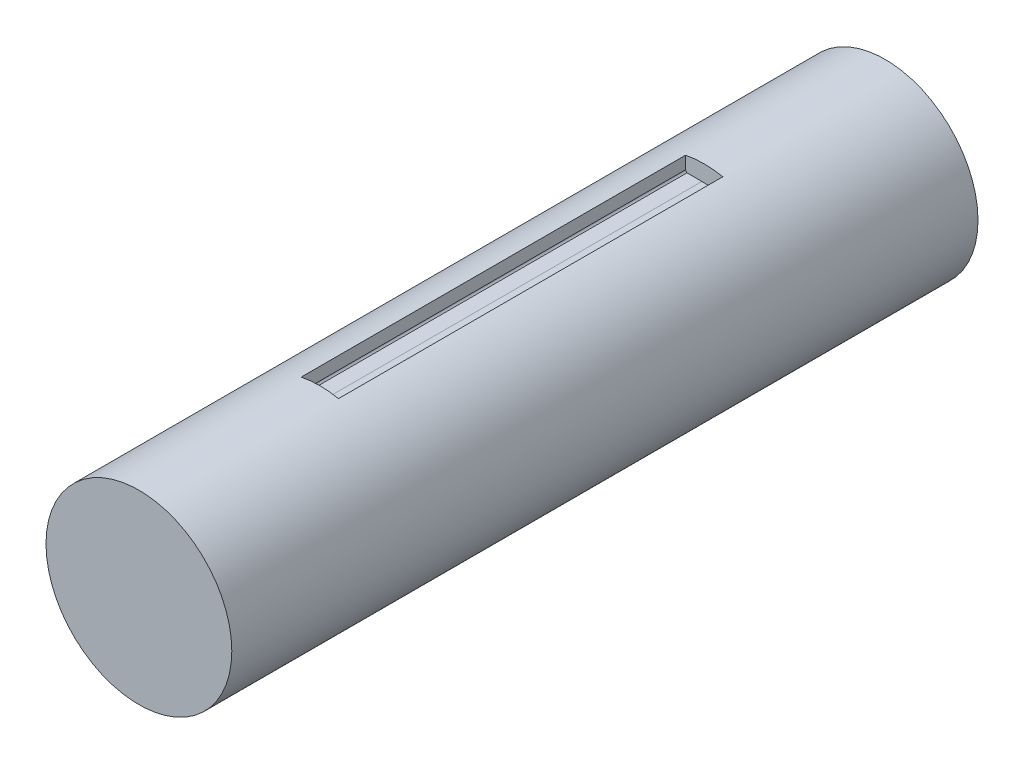
SolidWorks part; units mm, degrees
ref_plane "Ön Düzlem" through (0, 0, 0) normal (0, 0, 1) x (1, 0, 0)
ref_plane "Üst Düzlem" through (0, 0, 0) normal (0, 1, 0) x (1, 0, 0)
ref_plane "Sağ Düzlem" through (0, 0, 0) normal (1, 0, 0) x (0, 0, -1)
sketch "Model" plane through (0, 0, 0) normal (0, 0, 1) x (1, 0, 0)
  line L0 (-9.5, 79.7049) -> (9.5, 79.7049)
  line L1 (60.5945, 121.4987) -> (60.8885, 121.3363)
  line L2 (60.8885, 121.3363) -> (61.139, 121.1124)
  line L3 (61.139, 121.1124) -> (61.3334, 120.8385)
  line L4 (61.3334, 120.8385) -> (61.4619, 120.5282)
  line L5 (61.4619, 120.5282) -> (61.5182, 120.197)
  line L6 (61.5182, 120.197) -> (61.4993, 119.8617)
  line L7 (61.4993, 119.8617) -> (61.4063, 119.5389)
  line L8 (61.4063, 119.5389) -> (45.7726, 92.4605)
  line L9 (45.7726, 92.4605) -> (42.0525, 92.3778)
  line L10 (42.0525, 92.3778) -> (41.4785, 90.992)
  line L11 (58.0621, 81.4174) -> (58.9753, 82.6074)
  line L12 (58.9753, 82.6074) -> (57.1868, 85.8705)
  line L13 (57.1868, 85.8705) -> (72.8206, 112.9489)
  line L14 (72.8206, 112.9489) -> (73.0536, 113.1908)
  line L15 (73.0536, 113.1908) -> (73.3346, 113.3748)
  line L16 (73.3346, 113.3748) -> (73.6495, 113.4917)
  line L17 (73.6495, 113.4917) -> (73.9825, 113.5355)
  line L18 (73.9825, 113.5355) -> (74.317, 113.5041)
  line L19 (74.317, 113.5041) -> (74.636, 113.3991)
  line L20 (74.636, 113.3991) -> (74.9237, 113.2258)
  line L21 (74.9237, 113.2258) -> (89.976, 101.6758)
  line L22 (89.976, 101.6758) -> (90.2179, 101.4427)
  line L23 (90.2179, 101.4427) -> (90.4019, 101.1617)
  line L24 (90.4019, 101.1617) -> (90.5188, 100.8468)
  line L25 (90.5188, 100.8468) -> (90.5626, 100.5138)
  line L26 (90.5626, 100.5138) -> (90.5313, 100.1793)
  line L27 (90.5313, 100.1793) -> (90.4263, 99.8603)
  line L28 (90.4263, 99.8603) -> (90.2529, 99.5726)
  line L29 (90.2529, 99.5726) -> (68.1435, 77.4631)
  line L30 (68.1435, 77.4631) -> (64.5287, 78.3461)
  line L31 (64.5287, 78.3461) -> (63.6156, 77.1561)
  line L32 (77.1561, 63.6156) -> (78.3461, 64.5287)
  line L33 (78.3461, 64.5287) -> (77.4631, 68.1435)
  line L34 (77.4631, 68.1435) -> (99.5726, 90.2529)
  line L35 (99.5726, 90.2529) -> (99.8603, 90.4263)
  line L36 (99.8603, 90.4263) -> (100.1793, 90.5313)
  line L37 (100.1793, 90.5313) -> (100.5138, 90.5626)
  line L38 (100.5138, 90.5626) -> (100.8468, 90.5188)
  line L39 (100.8468, 90.5188) -> (101.1617, 90.4019)
  line L40 (101.1617, 90.4019) -> (101.4427, 90.2179)
  line L41 (101.4427, 90.2179) -> (101.6758, 89.976)
  line L42 (101.6758, 89.976) -> (113.2258, 74.9237)
  line L43 (113.2258, 74.9237) -> (113.3991, 74.636)
  line L44 (113.3991, 74.636) -> (113.5041, 74.317)
  line L45 (113.5041, 74.317) -> (113.5355, 73.9825)
  line L46 (113.5355, 73.9825) -> (113.4917, 73.6495)
  line L47 (113.4917, 73.6495) -> (113.3748, 73.3346)
  line L48 (113.3748, 73.3346) -> (113.1908, 73.0536)
  line L49 (113.1908, 73.0536) -> (112.9489, 72.8206)
  line L50 (112.9489, 72.8206) -> (85.8705, 57.1868)
  line L51 (85.8705, 57.1868) -> (82.6074, 58.9753)
  line L52 (82.6074, 58.9753) -> (81.4174, 58.0621)
  line L53 (90.992, 41.4785) -> (92.3778, 42.0525)
  line L54 (92.3778, 42.0525) -> (92.4605, 45.7726)
  line L55 (92.4605, 45.7726) -> (119.5389, 61.4063)
  line L56 (119.5389, 61.4063) -> (119.8617, 61.4993)
  line L57 (119.8617, 61.4993) -> (120.197, 61.5182)
  line L58 (120.197, 61.5182) -> (120.5282, 61.4619)
  line L59 (120.5282, 61.4619) -> (120.8385, 61.3334)
  line L60 (120.8385, 61.3334) -> (121.1124, 61.139)
  line L61 (121.1124, 61.139) -> (121.3363, 60.8885)
  line L62 (121.3363, 60.8885) -> (121.4987, 60.5945)
  line L63 (121.4987, 60.5945) -> (128.7594, 43.0658)
  line L64 (128.7594, 43.0658) -> (128.8524, 42.743)
  line L65 (128.8524, 42.743) -> (128.8712, 42.4076)
  line L66 (128.8712, 42.4076) -> (128.815, 42.0765)
  line L67 (128.815, 42.0765) -> (128.6864, 41.7662)
  line L68 (128.6864, 41.7662) -> (128.492, 41.4922)
  line L69 (128.492, 41.4922) -> (128.2416, 41.2684)
  line L70 (128.2416, 41.2684) -> (127.9476, 41.1059)
  line L71 (127.9476, 41.1059) -> (97.7455, 33.0133)
  line L72 (97.7455, 33.0133) -> (95.0566, 35.5853)
  line L73 (95.0566, 35.5853) -> (93.6707, 35.0113)
  line L74 (98.6269, 16.5147) -> (100.1141, 16.7105)
  line L75 (100.1141, 16.7105) -> (101.1568, 20.2824)
  line L76 (101.1568, 20.2824) -> (131.3588, 28.375)
  line L77 (131.3588, 28.375) -> (131.6947, 28.3813)
  line L78 (131.6947, 28.3813) -> (132.0235, 28.3127)
  line L79 (132.0235, 28.3127) -> (132.3288, 28.1726)
  line L80 (132.3288, 28.1726) -> (132.5953, 27.9682)
  line L81 (132.5953, 27.9682) -> (132.8096, 27.7095)
  line L82 (132.8096, 27.7095) -> (132.9609, 27.4097)
  line L83 (132.9609, 27.4097) -> (133.0418, 27.0836)
  line L84 (133.0418, 27.0836) -> (135.5183, 8.273)
  line L85 (135.5183, 8.273) -> (135.5246, 7.9371)
  line L86 (135.5246, 7.9371) -> (135.4559, 7.6083)
  line L87 (135.4559, 7.6083) -> (135.3159, 7.303)
  line L88 (135.3159, 7.303) -> (135.1114, 7.0365)
  line L89 (135.1114, 7.0365) -> (134.8528, 6.8222)
  line L90 (134.8528, 6.8222) -> (134.5529, 6.6709)
  line L91 (134.5529, 6.6709) -> (134.2269, 6.59)
  line L92 (134.2269, 6.59) -> (102.9594, 6.59)
  line L93 (102.9594, 6.59) -> (101.0278, 9.7704)
  line L94 (101.0278, 9.7704) -> (99.5406, 9.5746)
  line L95 (99.5406, -9.5746) -> (101.0278, -9.7704)
  line L96 (101.0278, -9.7704) -> (102.9594, -6.59)
  line L97 (102.9594, -6.59) -> (134.2269, -6.59)
  line L98 (134.2269, -6.59) -> (134.5529, -6.6709)
  line L99 (134.5529, -6.6709) -> (134.8528, -6.8222)
  line L100 (134.8528, -6.8222) -> (135.1114, -7.0365)
  line L101 (135.1114, -7.0365) -> (135.3159, -7.303)
  line L102 (135.3159, -7.303) -> (135.4559, -7.6083)
  line L103 (135.4559, -7.6083) -> (135.5246, -7.9371)
  line L104 (135.5246, -7.9371) -> (135.5183, -8.273)
  line L105 (135.5183, -8.273) -> (133.0418, -27.0836)
  line L106 (133.0418, -27.0836) -> (132.9609, -27.4097)
  line L107 (132.9609, -27.4097) -> (132.8096, -27.7095)
  line L108 (132.8096, -27.7095) -> (132.5953, -27.9682)
  line L109 (132.5953, -27.9682) -> (132.3288, -28.1726)
  line L110 (132.3288, -28.1726) -> (132.0235, -28.3127)
  line L111 (132.0235, -28.3127) -> (131.6947, -28.3813)
  line L112 (131.6947, -28.3813) -> (131.3588, -28.375)
  line L113 (131.3588, -28.375) -> (101.1568, -20.2824)
  line L114 (101.1568, -20.2824) -> (100.1141, -16.7105)
  line L115 (100.1141, -16.7105) -> (98.6269, -16.5147)
  line L116 (93.6707, -35.0113) -> (95.0566, -35.5853)
  line L117 (95.0566, -35.5853) -> (97.7455, -33.0133)
  line L118 (97.7455, -33.0133) -> (127.9476, -41.1059)
  line L119 (127.9476, -41.1059) -> (128.2416, -41.2684)
  line L120 (128.2416, -41.2684) -> (128.492, -41.4922)
  line L121 (128.492, -41.4922) -> (128.6864, -41.7662)
  line L122 (128.6864, -41.7662) -> (128.815, -42.0765)
  line L123 (128.815, -42.0765) -> (128.8712, -42.4076)
  line L124 (128.8712, -42.4076) -> (128.8524, -42.743)
  line L125 (128.8524, -42.743) -> (128.7594, -43.0658)
  line L126 (128.7594, -43.0658) -> (121.4987, -60.5945)
  line L127 (121.4987, -60.5945) -> (121.3363, -60.8885)
  line L128 (121.3363, -60.8885) -> (121.1124, -61.139)
  line L129 (121.1124, -61.139) -> (120.8385, -61.3334)
  line L130 (120.8385, -61.3334) -> (120.5282, -61.4619)
  line L131 (120.5282, -61.4619) -> (120.197, -61.5182)
  line L132 (120.197, -61.5182) -> (119.8617, -61.4993)
  line L133 (119.8617, -61.4993) -> (119.5389, -61.4063)
  line L134 (119.5389, -61.4063) -> (92.4605, -45.7726)
  line L135 (92.4605, -45.7726) -> (92.3778, -42.0525)
  line L136 (92.3778, -42.0525) -> (90.992, -41.4785)
  line L137 (81.4174, -58.0621) -> (82.6074, -58.9753)
  line L138 (82.6074, -58.9753) -> (85.8705, -57.1868)
  line L139 (85.8705, -57.1868) -> (112.9489, -72.8206)
  line L140 (112.9489, -72.8206) -> (113.1908, -73.0536)
  line L141 (113.1908, -73.0536) -> (113.3748, -73.3346)
  line L142 (113.3748, -73.3346) -> (113.4917, -73.6495)
  line L143 (113.4917, -73.6495) -> (113.5355, -73.9825)
  line L144 (113.5355, -73.9825) -> (113.5041, -74.317)
  line L145 (113.5041, -74.317) -> (113.3991, -74.636)
  line L146 (113.3991, -74.636) -> (113.2258, -74.9237)
  line L147 (113.2258, -74.9237) -> (101.6758, -89.976)
  line L148 (101.6758, -89.976) -> (101.4427, -90.2179)
  line L149 (101.4427, -90.2179) -> (101.1617, -90.4019)
  line L150 (101.1617, -90.4019) -> (100.8468, -90.5188)
  line L151 (100.8468, -90.5188) -> (100.5138, -90.5626)
  line L152 (100.5138, -90.5626) -> (100.1793, -90.5313)
  line L153 (100.1793, -90.5313) -> (99.8603, -90.4263)
  line L154 (99.8603, -90.4263) -> (99.5726, -90.2529)
  line L155 (99.5726, -90.2529) -> (77.4631, -68.1435)
  line L156 (77.4631, -68.1435) -> (78.3461, -64.5287)
  line L157 (78.3461, -64.5287) -> (77.1561, -63.6156)
  line L158 (63.6156, -77.1561) -> (64.5287, -78.3461)
  line L159 (64.5287, -78.3461) -> (68.1435, -77.4631)
  line L160 (68.1435, -77.4631) -> (90.2529, -99.5726)
  line L161 (90.2529, -99.5726) -> (90.4263, -99.8603)
  line L162 (90.4263, -99.8603) -> (90.5313, -100.1793)
  line L163 (90.5313, -100.1793) -> (90.5626, -100.5138)
  line L164 (90.5626, -100.5138) -> (90.5188, -100.8468)
  line L165 (90.5188, -100.8468) -> (90.4019, -101.1617)
  line L166 (90.4019, -101.1617) -> (90.2179, -101.4427)
  line L167 (90.2179, -101.4427) -> (89.976, -101.6758)
  line L168 (89.976, -101.6758) -> (74.9237, -113.2258)
  line L169 (74.9237, -113.2258) -> (74.636, -113.3991)
  line L170 (74.636, -113.3991) -> (74.317, -113.5041)
  line L171 (74.317, -113.5041) -> (73.9825, -113.5355)
  line L172 (73.9825, -113.5355) -> (73.6495, -113.4917)
  line L173 (73.6495, -113.4917) -> (73.3346, -113.3748)
  line L174 (73.3346, -113.3748) -> (73.0536, -113.1908)
  line L175 (73.0536, -113.1908) -> (72.8206, -112.9489)
  line L176 (72.8206, -112.9489) -> (57.1868, -85.8705)
  line L177 (57.1868, -85.8705) -> (58.9753, -82.6074)
  line L178 (58.9753, -82.6074) -> (58.0621, -81.4174)
  line L179 (41.4785, -90.992) -> (42.0525, -92.3778)
  line L180 (42.0525, -92.3778) -> (45.7726, -92.4605)
  line L181 (45.7726, -92.4605) -> (61.4063, -119.5389)
  line L182 (61.4063, -119.5389) -> (61.4993, -119.8617)
  line L183 (61.4993, -119.8617) -> (61.5182, -120.197)
  line L184 (61.5182, -120.197) -> (61.4619, -120.5282)
  line L185 (61.4619, -120.5282) -> (61.3334, -120.8385)
  line L186 (61.3334, -120.8385) -> (61.139, -121.1124)
  line L187 (61.139, -121.1124) -> (60.8885, -121.3363)
  line L188 (60.8885, -121.3363) -> (60.5945, -121.4987)
  line L189 (60.5945, -121.4987) -> (43.0658, -128.7594)
  line L190 (43.0658, -128.7594) -> (42.743, -128.8524)
  line L191 (42.743, -128.8524) -> (42.4076, -128.8712)
  line L192 (42.4076, -128.8712) -> (42.0765, -128.815)
  line L193 (42.0765, -128.815) -> (41.7662, -128.6864)
  line L194 (41.7662, -128.6864) -> (41.4922, -128.492)
  line L195 (41.4922, -128.492) -> (41.2684, -128.2416)
  line L196 (41.2684, -128.2416) -> (41.1059, -127.9476)
  line L197 (41.1059, -127.9476) -> (33.0133, -97.7455)
  line L198 (33.0133, -97.7455) -> (35.5853, -95.0566)
  line L199 (35.5853, -95.0566) -> (35.0113, -93.6707)
  line L200 (16.5147, -98.6269) -> (16.7105, -100.1141)
  line L201 (16.7105, -100.1141) -> (20.2824, -101.1568)
  line L202 (20.2824, -101.1568) -> (28.375, -131.3588)
  line L203 (28.375, -131.3588) -> (28.3813, -131.6947)
  line L204 (28.3813, -131.6947) -> (28.3127, -132.0235)
  line L205 (28.3127, -132.0235) -> (28.1726, -132.3288)
  line L206 (28.1726, -132.3288) -> (27.9682, -132.5953)
  line L207 (27.9682, -132.5953) -> (27.7095, -132.8096)
  line L208 (27.7095, -132.8096) -> (27.4097, -132.9609)
  line L209 (27.4097, -132.9609) -> (27.0836, -133.0418)
  line L210 (27.0836, -133.0418) -> (8.273, -135.5183)
  line L211 (8.273, -135.5183) -> (7.9371, -135.5246)
  line L212 (7.9371, -135.5246) -> (7.6083, -135.4559)
  line L213 (7.6083, -135.4559) -> (7.303, -135.3159)
  line L214 (7.303, -135.3159) -> (7.0365, -135.1114)
  line L215 (7.0365, -135.1114) -> (6.8222, -134.8528)
  line L216 (6.8222, -134.8528) -> (6.6709, -134.5529)
  line L217 (6.6709, -134.5529) -> (6.59, -134.2269)
  line L218 (6.59, -134.2269) -> (6.59, -102.9594)
  line L219 (6.59, -102.9594) -> (9.7704, -101.0278)
  line L220 (9.7704, -101.0278) -> (9.5746, -99.5406)
  line L221 (-9.5746, -99.5406) -> (-9.7704, -101.0278)
  line L222 (-9.7704, -101.0278) -> (-6.59, -102.9594)
  line L223 (-6.59, -102.9594) -> (-6.59, -134.2269)
  line L224 (-6.59, -134.2269) -> (-6.6709, -134.5529)
  line L225 (-6.6709, -134.5529) -> (-6.8222, -134.8528)
  line L226 (-6.8222, -134.8528) -> (-7.0365, -135.1114)
  line L227 (-7.0365, -135.1114) -> (-7.303, -135.3159)
  line L228 (-7.303, -135.3159) -> (-7.6083, -135.4559)
  line L229 (-7.6083, -135.4559) -> (-7.9371, -135.5246)
  line L230 (-7.9371, -135.5246) -> (-8.273, -135.5183)
  line L231 (-8.273, -135.5183) -> (-27.0836, -133.0418)
  line L232 (-27.0836, -133.0418) -> (-27.4097, -132.9609)
  line L233 (-27.4097, -132.9609) -> (-27.7095, -132.8096)
  line L234 (-27.7095, -132.8096) -> (-27.9682, -132.5953)
  line L235 (-27.9682, -132.5953) -> (-28.1726, -132.3288)
  line L236 (-28.1726, -132.3288) -> (-28.3127, -132.0235)
  line L237 (-28.3127, -132.0235) -> (-28.3813, -131.6947)
  line L238 (-28.3813, -131.6947) -> (-28.375, -131.3588)
  line L239 (-28.375, -131.3588) -> (-20.2824, -101.1568)
  line L240 (-20.2824, -101.1568) -> (-16.7105, -100.1141)
  line L241 (-16.7105, -100.1141) -> (-16.5147, -98.6269)
  line L242 (-35.0113, -93.6707) -> (-35.5853, -95.0566)
  line L243 (-35.5853, -95.0566) -> (-33.0133, -97.7455)
  line L244 (-33.0133, -97.7455) -> (-41.1059, -127.9476)
  line L245 (-41.1059, -127.9476) -> (-41.2684, -128.2416)
  line L246 (-41.2684, -128.2416) -> (-41.4922, -128.492)
  line L247 (-41.4922, -128.492) -> (-41.7662, -128.6864)
  line L248 (-41.7662, -128.6864) -> (-42.0765, -128.815)
  line L249 (-42.0765, -128.815) -> (-42.4076, -128.8712)
  line L250 (-42.4076, -128.8712) -> (-42.743, -128.8524)
  line L251 (-42.743, -128.8524) -> (-43.0658, -128.7594)
  line L252 (-43.0658, -128.7594) -> (-60.5945, -121.4987)
  line L253 (-60.5945, -121.4987) -> (-60.8885, -121.3363)
  line L254 (-60.8885, -121.3363) -> (-61.139, -121.1124)
  line L255 (-61.139, -121.1124) -> (-61.3334, -120.8385)
  line L256 (-61.3334, -120.8385) -> (-61.4619, -120.5282)
  line L257 (-61.4619, -120.5282) -> (-61.5182, -120.197)
  line L258 (-61.5182, -120.197) -> (-61.4993, -119.8617)
  line L259 (-61.4993, -119.8617) -> (-61.4063, -119.5389)
  line L260 (-61.4063, -119.5389) -> (-45.7726, -92.4605)
  line L261 (-45.7726, -92.4605) -> (-42.0525, -92.3778)
  line L262 (-42.0525, -92.3778) -> (-41.4785, -90.992)
  line L263 (-58.0621, -81.4174) -> (-58.9753, -82.6074)
  line L264 (-58.9753, -82.6074) -> (-57.1868, -85.8705)
  line L265 (-57.1868, -85.8705) -> (-72.8206, -112.9489)
  line L266 (-72.8206, -112.9489) -> (-73.0536, -113.1908)
  line L267 (-73.0536, -113.1908) -> (-73.3346, -113.3748)
  line L268 (-73.3346, -113.3748) -> (-73.6495, -113.4917)
  line L269 (-73.6495, -113.4917) -> (-73.9825, -113.5355)
  line L270 (-73.9825, -113.5355) -> (-74.317, -113.5041)
  line L271 (-74.317, -113.5041) -> (-74.636, -113.3991)
  line L272 (-74.636, -113.3991) -> (-74.9237, -113.2258)
  line L273 (-74.9237, -113.2258) -> (-89.976, -101.6758)
  line L274 (-89.976, -101.6758) -> (-90.2179, -101.4427)
  line L275 (-90.2179, -101.4427) -> (-90.4019, -101.1617)
  line L276 (-90.4019, -101.1617) -> (-90.5188, -100.8468)
  line L277 (-90.5188, -100.8468) -> (-90.5626, -100.5138)
  line L278 (-90.5626, -100.5138) -> (-90.5313, -100.1793)
  line L279 (-90.5313, -100.1793) -> (-90.4263, -99.8603)
  line L280 (-90.4263, -99.8603) -> (-90.2529, -99.5726)
  line L281 (-90.2529, -99.5726) -> (-68.1435, -77.4631)
  line L282 (-68.1435, -77.4631) -> (-64.5287, -78.3461)
  line L283 (-64.5287, -78.3461) -> (-63.6156, -77.1561)
  line L284 (-77.1561, -63.6156) -> (-78.3461, -64.5287)
  line L285 (-78.3461, -64.5287) -> (-77.4631, -68.1435)
  line L286 (-77.4631, -68.1435) -> (-99.5726, -90.2529)
  line L287 (-99.5726, -90.2529) -> (-99.8603, -90.4263)
  line L288 (-99.8603, -90.4263) -> (-100.1793, -90.5313)
  line L289 (-100.1793, -90.5313) -> (-100.5138, -90.5626)
  line L290 (-100.5138, -90.5626) -> (-100.8468, -90.5188)
  line L291 (-100.8468, -90.5188) -> (-101.1617, -90.4019)
  line L292 (-101.1617, -90.4019) -> (-101.4427, -90.2179)
  line L293 (-101.4427, -90.2179) -> (-101.6758, -89.976)
  line L294 (-101.6758, -89.976) -> (-113.2258, -74.9237)
  line L295 (-113.2258, -74.9237) -> (-113.3991, -74.636)
  line L296 (-113.3991, -74.636) -> (-113.5041, -74.317)
  line L297 (-113.5041, -74.317) -> (-113.5355, -73.9825)
  line L298 (-113.5355, -73.9825) -> (-113.4917, -73.6495)
  line L299 (-113.4917, -73.6495) -> (-113.3748, -73.3346)
  line L300 (-113.3748, -73.3346) -> (-113.1908, -73.0536)
  line L301 (-113.1908, -73.0536) -> (-112.9489, -72.8206)
  line L302 (-112.9489, -72.8206) -> (-85.8705, -57.1868)
  line L303 (-85.8705, -57.1868) -> (-82.6074, -58.9753)
  line L304 (-82.6074, -58.9753) -> (-81.4174, -58.0621)
  line L305 (-90.992, -41.4785) -> (-92.3778, -42.0525)
  line L306 (-92.3778, -42.0525) -> (-92.4605, -45.7726)
  line L307 (-92.4605, -45.7726) -> (-119.5389, -61.4063)
  line L308 (-119.5389, -61.4063) -> (-119.8617, -61.4993)
  line L309 (-119.8617, -61.4993) -> (-120.197, -61.5182)
  line L310 (-120.197, -61.5182) -> (-120.5282, -61.4619)
  line L311 (-120.5282, -61.4619) -> (-120.8385, -61.3334)
  line L312 (-120.8385, -61.3334) -> (-121.1124, -61.139)
  line L313 (-121.1124, -61.139) -> (-121.3363, -60.8885)
  line L314 (-121.3363, -60.8885) -> (-121.4987, -60.5945)
  line L315 (-121.4987, -60.5945) -> (-128.7594, -43.0658)
  line L316 (-128.7594, -43.0658) -> (-128.8524, -42.743)
  line L317 (-128.8524, -42.743) -> (-128.8712, -42.4076)
  line L318 (-128.8712, -42.4076) -> (-128.815, -42.0765)
  line L319 (-128.815, -42.0765) -> (-128.6864, -41.7662)
  line L320 (-128.6864, -41.7662) -> (-128.492, -41.4922)
  line L321 (-128.492, -41.4922) -> (-128.2416, -41.2684)
  line L322 (-128.2416, -41.2684) -> (-127.9476, -41.1059)
  line L323 (-127.9476, -41.1059) -> (-97.7455, -33.0133)
  line L324 (-97.7455, -33.0133) -> (-95.0566, -35.5853)
  line L325 (-95.0566, -35.5853) -> (-93.6707, -35.0113)
  line L326 (-98.6269, -16.5147) -> (-100.1141, -16.7105)
  line L327 (-100.1141, -16.7105) -> (-101.1568, -20.2824)
  line L328 (-101.1568, -20.2824) -> (-131.3588, -28.375)
  line L329 (-131.3588, -28.375) -> (-131.6947, -28.3813)
  line L330 (-131.6947, -28.3813) -> (-132.0235, -28.3127)
  line L331 (-132.0235, -28.3127) -> (-132.3288, -28.1726)
  line L332 (-132.3288, -28.1726) -> (-132.5953, -27.9682)
  line L333 (-132.5953, -27.9682) -> (-132.8096, -27.7095)
  line L334 (-132.8096, -27.7095) -> (-132.9609, -27.4097)
  line L335 (-132.9609, -27.4097) -> (-133.0418, -27.0836)
  line L336 (-133.0418, -27.0836) -> (-135.5183, -8.273)
  line L337 (-135.5183, -8.273) -> (-135.5246, -7.9371)
  line L338 (-135.5246, -7.9371) -> (-135.4559, -7.6083)
  line L339 (-135.4559, -7.6083) -> (-135.3159, -7.303)
  line L340 (-135.3159, -7.303) -> (-135.1114, -7.0365)
  line L341 (-135.1114, -7.0365) -> (-134.8528, -6.8222)
  line L342 (-134.8528, -6.8222) -> (-134.5529, -6.6709)
  line L343 (-134.5529, -6.6709) -> (-134.2269, -6.59)
  line L344 (-134.2269, -6.59) -> (-102.9594, -6.59)
  line L345 (-102.9594, -6.59) -> (-101.0278, -9.7704)
  line L346 (-101.0278, -9.7704) -> (-99.5406, -9.5746)
  line L347 (-99.5406, 9.5746) -> (-101.0278, 9.7704)
  line L348 (-101.0278, 9.7704) -> (-102.9594, 6.59)
  line L349 (-102.9594, 6.59) -> (-134.2269, 6.59)
  line L350 (-134.2269, 6.59) -> (-134.5529, 6.6709)
  line L351 (-134.5529, 6.6709) -> (-134.8528, 6.8222)
  line L352 (-134.8528, 6.8222) -> (-135.1114, 7.0365)
  line L353 (-135.1114, 7.0365) -> (-135.3159, 7.303)
  line L354 (-135.3159, 7.303) -> (-135.4559, 7.6083)
  line L355 (-135.4559, 7.6083) -> (-135.5246, 7.9371)
  line L356 (-135.5246, 7.9371) -> (-135.5183, 8.273)
  line L357 (-135.5183, 8.273) -> (-133.0418, 27.0836)
  line L358 (-133.0418, 27.0836) -> (-132.9609, 27.4097)
  line L359 (-132.9609, 27.4097) -> (-132.8096, 27.7095)
  line L360 (-132.8096, 27.7095) -> (-132.5953, 27.9682)
  line L361 (-132.5953, 27.9682) -> (-132.3288, 28.1726)
  line L362 (-132.3288, 28.1726) -> (-132.0235, 28.3127)
  line L363 (-132.0235, 28.3127) -> (-131.6947, 28.3813)
  line L364 (-131.6947, 28.3813) -> (-131.3588, 28.375)
  line L365 (-131.3588, 28.375) -> (-101.1568, 20.2824)
  line L366 (-101.1568, 20.2824) -> (-100.1141, 16.7105)
  line L367 (-100.1141, 16.7105) -> (-98.6269, 16.5147)
  line L368 (-93.6707, 35.0113) -> (-95.0566, 35.5853)
  line L369 (-95.0566, 35.5853) -> (-97.7455, 33.0133)
  line L370 (-97.7455, 33.0133) -> (-127.9476, 41.1059)
  line L371 (-127.9476, 41.1059) -> (-128.2416, 41.2684)
  line L372 (-128.2416, 41.2684) -> (-128.492, 41.4922)
  line L373 (-128.492, 41.4922) -> (-128.6864, 41.7662)
  line L374 (-128.6864, 41.7662) -> (-128.815, 42.0765)
  line L375 (-128.815, 42.0765) -> (-128.8712, 42.4076)
  line L376 (-128.8712, 42.4076) -> (-128.8524, 42.743)
  line L377 (-128.8524, 42.743) -> (-128.7594, 43.0658)
  line L378 (-128.7594, 43.0658) -> (-121.4987, 60.5945)
  line L379 (-121.4987, 60.5945) -> (-121.3363, 60.8885)
  line L380 (-121.3363, 60.8885) -> (-121.1124, 61.139)
  line L381 (-121.1124, 61.139) -> (-120.8385, 61.3334)
  line L382 (-120.8385, 61.3334) -> (-120.5282, 61.4619)
  line L383 (-120.5282, 61.4619) -> (-120.197, 61.5182)
  line L384 (-120.197, 61.5182) -> (-119.8617, 61.4993)
  line L385 (-119.8617, 61.4993) -> (-119.5389, 61.4063)
  line L386 (-119.5389, 61.4063) -> (-92.4605, 45.7726)
  line L387 (-92.4605, 45.7726) -> (-92.3778, 42.0525)
  line L388 (-92.3778, 42.0525) -> (-90.992, 41.4785)
  line L389 (-81.4174, 58.0621) -> (-82.6074, 58.9753)
  line L390 (-82.6074, 58.9753) -> (-85.8705, 57.1868)
  line L391 (-85.8705, 57.1868) -> (-112.9489, 72.8206)
  line L392 (-112.9489, 72.8206) -> (-113.1908, 73.0536)
  line L393 (-113.1908, 73.0536) -> (-113.3748, 73.3346)
  line L394 (-113.3748, 73.3346) -> (-113.4917, 73.6495)
  line L395 (-113.4917, 73.6495) -> (-113.5355, 73.9825)
  line L396 (-113.5355, 73.9825) -> (-113.5041, 74.317)
  line L397 (-113.5041, 74.317) -> (-113.3991, 74.636)
  line L398 (-113.3991, 74.636) -> (-113.2258, 74.9237)
  line L399 (-113.2258, 74.9237) -> (-101.6758, 89.976)
  line L400 (-101.6758, 89.976) -> (-101.4427, 90.2179)
  line L401 (-101.4427, 90.2179) -> (-101.1617, 90.4019)
  line L402 (-101.1617, 90.4019) -> (-100.8468, 90.5188)
  line L403 (-100.8468, 90.5188) -> (-100.5138, 90.5626)
  line L404 (-100.5138, 90.5626) -> (-100.1793, 90.5313)
  line L405 (-100.1793, 90.5313) -> (-99.8603, 90.4263)
  line L406 (-99.8603, 90.4263) -> (-99.5726, 90.2529)
  line L407 (-99.5726, 90.2529) -> (-77.4631, 68.1435)
  line L408 (-77.4631, 68.1435) -> (-78.3461, 64.5287)
  line L409 (-78.3461, 64.5287) -> (-77.1561, 63.6156)
  line L410 (-63.6156, 77.1561) -> (-64.5287, 78.3461)
  line L411 (-64.5287, 78.3461) -> (-68.1435, 77.4631)
  line L412 (-68.1435, 77.4631) -> (-90.2529, 99.5726)
  line L413 (-90.2529, 99.5726) -> (-90.4263, 99.8603)
  line L414 (-90.4263, 99.8603) -> (-90.5313, 100.1793)
  line L415 (-90.5313, 100.1793) -> (-90.5626, 100.5138)
  line L416 (-90.5626, 100.5138) -> (-90.5188, 100.8468)
  line L417 (-90.5188, 100.8468) -> (-90.4019, 101.1617)
  line L418 (-90.4019, 101.1617) -> (-90.2179, 101.4427)
  line L419 (-90.2179, 101.4427) -> (-89.976, 101.6758)
  line L420 (-89.976, 101.6758) -> (-74.9237, 113.2258)
  line L421 (-74.9237, 113.2258) -> (-74.636, 113.3991)
  line L422 (-74.636, 113.3991) -> (-74.317, 113.5041)
  line L423 (-74.317, 113.5041) -> (-73.9825, 113.5355)
  line L424 (-73.9825, 113.5355) -> (-73.6495, 113.4917)
  line L425 (-73.6495, 113.4917) -> (-73.3346, 113.3748)
  line L426 (-73.3346, 113.3748) -> (-73.0536, 113.1908)
  line L427 (-73.0536, 113.1908) -> (-72.8206, 112.9489)
  line L428 (-72.8206, 112.9489) -> (-57.1868, 85.8705)
  line L429 (-57.1868, 85.8705) -> (-58.9753, 82.6074)
  line L430 (-58.9753, 82.6074) -> (-58.0621, 81.4174)
  line L431 (-41.4785, 90.992) -> (-42.0525, 92.3778)
  line L432 (-42.0525, 92.3778) -> (-45.7726, 92.4605)
  line L433 (-45.7726, 92.4605) -> (-61.4063, 119.5389)
  line L434 (-61.4063, 119.5389) -> (-61.4993, 119.8617)
  line L435 (-61.4993, 119.8617) -> (-61.5182, 120.197)
  line L436 (-61.5182, 120.197) -> (-61.4619, 120.5282)
  line L437 (-61.4619, 120.5282) -> (-61.3334, 120.8385)
  line L438 (-61.3334, 120.8385) -> (-61.139, 121.1124)
  line L439 (-61.139, 121.1124) -> (-60.8885, 121.3363)
  line L440 (-60.8885, 121.3363) -> (-60.5945, 121.4987)
  line L441 (-60.5945, 121.4987) -> (-43.0658, 128.7594)
  line L442 (-43.0658, 128.7594) -> (-42.743, 128.8524)
  line L443 (-42.743, 128.8524) -> (-42.4076, 128.8712)
  line L444 (-42.4076, 128.8712) -> (-42.0765, 128.815)
  line L445 (-42.0765, 128.815) -> (-41.7662, 128.6864)
  line L446 (-41.7662, 128.6864) -> (-41.4922, 128.492)
  line L447 (-41.4922, 128.492) -> (-41.2684, 128.2416)
  line L448 (-41.2684, 128.2416) -> (-41.1059, 127.9476)
  line L449 (-41.1059, 127.9476) -> (-33.0133, 97.7455)
  line L450 (-33.0133, 97.7455) -> (-35.5853, 95.0566)
  line L451 (-35.5853, 95.0566) -> (-35.0113, 93.6707)
  line L452 (-16.5147, 98.6269) -> (-16.7105, 100.1141)
  line L453 (-16.7105, 100.1141) -> (-20.2824, 101.1568)
  line L454 (-20.2824, 101.1568) -> (-28.375, 131.3588)
  line L455 (-28.375, 131.3588) -> (-28.3813, 131.6947)
  line L456 (-28.3813, 131.6947) -> (-28.3127, 132.0235)
  line L457 (-28.3127, 132.0235) -> (-28.1726, 132.3288)
  line L458 (-28.1726, 132.3288) -> (-27.9682, 132.5953)
  line L459 (-27.9682, 132.5953) -> (-27.7095, 132.8096)
  line L460 (-27.7095, 132.8096) -> (-27.4097, 132.9609)
  line L461 (-27.4097, 132.9609) -> (-27.0836, 133.0418)
  line L462 (-27.0836, 133.0418) -> (-8.273, 135.5183)
  line L463 (-8.273, 135.5183) -> (-7.9371, 135.5246)
  line L464 (-7.9371, 135.5246) -> (-7.6083, 135.4559)
  line L465 (-7.6083, 135.4559) -> (-7.303, 135.3159)
  line L466 (-7.303, 135.3159) -> (-7.0365, 135.1114)
  line L467 (-7.0365, 135.1114) -> (-6.8222, 134.8528)
  line L468 (-6.8222, 134.8528) -> (-6.6709, 134.5529)
  line L469 (-6.6709, 134.5529) -> (-6.59, 134.2269)
  line L470 (-6.59, 134.2269) -> (-6.59, 102.9594)
  line L471 (-6.59, 102.9594) -> (-9.7704, 101.0278)
  line L472 (-9.7704, 101.0278) -> (-9.5746, 99.5406)
  line L473 (9.5746, 99.5406) -> (9.7704, 101.0278)
  line L474 (9.7704, 101.0278) -> (6.59, 102.9594)
  line L475 (6.59, 102.9594) -> (6.59, 134.2269)
  line L476 (6.59, 134.2269) -> (6.6709, 134.5529)
  line L477 (6.6709, 134.5529) -> (6.8222, 134.8528)
  line L478 (6.8222, 134.8528) -> (7.0365, 135.1114)
  line L479 (7.0365, 135.1114) -> (7.303, 135.3159)
  line L480 (7.303, 135.3159) -> (7.6083, 135.4559)
  line L481 (7.6083, 135.4559) -> (7.9371, 135.5246)
  line L482 (7.9371, 135.5246) -> (8.273, 135.5183)
  line L483 (8.273, 135.5183) -> (27.0836, 133.0418)
  line L484 (27.0836, 133.0418) -> (27.4097, 132.9609)
  line L485 (27.4097, 132.9609) -> (27.7095, 132.8096)
  line L486 (27.7095, 132.8096) -> (27.9682, 132.5953)
  line L487 (27.9682, 132.5953) -> (28.1726, 132.3288)
  line L488 (28.1726, 132.3288) -> (28.3127, 132.0235)
  line L489 (28.3127, 132.0235) -> (28.3813, 131.6947)
  line L490 (28.3813, 131.6947) -> (28.375, 131.3588)
  line L491 (28.375, 131.3588) -> (20.2824, 101.1568)
  line L492 (20.2824, 101.1568) -> (16.7105, 100.1141)
  line L493 (16.7105, 100.1141) -> (16.5147, 98.6269)
  line L494 (35.0113, 93.6707) -> (35.5853, 95.0566)
  line L495 (35.5853, 95.0566) -> (33.0133, 97.7455)
  line L496 (33.0133, 97.7455) -> (41.1059, 127.9476)
  line L497 (41.1059, 127.9476) -> (41.2684, 128.2416)
  line L498 (41.2684, 128.2416) -> (41.4922, 128.492)
  line L499 (41.4922, 128.492) -> (41.7662, 128.6864)
  line L500 (41.7662, 128.6864) -> (42.0765, 128.815)
  line L501 (42.0765, 128.815) -> (42.4076, 128.8712)
  line L502 (42.4076, 128.8712) -> (42.743, 128.8524)
  line L503 (42.743, 128.8524) -> (43.0658, 128.7594)
  line L504 (43.0658, 128.7594) -> (60.5945, 121.4987)
  line L505 (-9.5, 80.2049) -> (9.5, 80.2049)
  line L506 (10.5, 80.7049) -> (10.5, 83.8451)
  line L507 (10.5, -80.7049) -> (10.5, -83.8451)
  line L508 (27.7776, -94.5021) -> (26.5086, -90.1848)
  line L509 (2.6574, -93.9624) -> (2.7847, -98.4606)
  line L510 (-27.7776, 94.5021) -> (-26.5086, 90.1848)
  line L511 (-2.6574, 93.9624) -> (-2.7847, 98.4606)
  line L512 (94.5021, 27.7776) -> (90.1848, 26.5086)
  line L513 (93.9624, 2.6574) -> (98.4606, 2.7847)
  line L514 (-94.5021, -27.7776) -> (-90.1848, -26.5086)
  line L515 (-93.9624, -2.6574) -> (-98.4606, -2.7847)
  line L516 (55.6209, -81.2931) -> (53.0798, -77.5792)
  line L517 (31.5634, -88.5424) -> (33.0744, -92.7811)
  line L518 (-55.6209, 81.2931) -> (-53.0798, 77.5792)
  line L519 (-31.5634, 88.5424) -> (-33.0744, 92.7811)
  line L520 (81.2931, 55.6209) -> (77.5792, 53.0798)
  line L521 (88.5424, 31.5634) -> (92.7811, 33.0744)
  line L522 (-81.2931, -55.6209) -> (-77.5792, -53.0798)
  line L523 (-88.5424, -31.5634) -> (-92.7811, -33.0744)
  line L524 (78.0195, -60.1265) -> (74.4552, -57.3796)
  line L525 (57.3796, -74.4552) -> (60.1265, -78.0195)
  line L526 (-78.0195, 60.1265) -> (-74.4552, 57.3796)
  line L527 (-57.3796, 74.4552) -> (-60.1265, 78.0195)
  line L528 (60.1265, 78.0195) -> (57.3796, 74.4552)
  line L529 (74.4552, 57.3796) -> (78.0195, 60.1265)
  line L530 (-60.1265, -78.0195) -> (-57.3796, -74.4552)
  line L531 (-74.4552, -57.3796) -> (-78.0195, -60.1265)
  line L532 (92.7811, -33.0744) -> (88.5424, -31.5634)
  line L533 (77.5792, -53.0798) -> (81.2931, -55.6209)
  line L534 (-92.7811, 33.0744) -> (-88.5424, 31.5634)
  line L535 (-77.5792, 53.0798) -> (-81.2931, 55.6209)
  line L536 (33.0744, 92.7811) -> (31.5634, 88.5424)
  line L537 (53.0798, 77.5792) -> (55.6209, 81.2931)
  line L538 (-33.0744, -92.7811) -> (-31.5634, -88.5424)
  line L539 (-53.0798, -77.5792) -> (-55.6209, -81.2931)
  line L540 (98.4606, -2.7847) -> (93.9624, -2.6574)
  line L541 (90.1848, -26.5086) -> (94.5021, -27.7776)
  line L542 (-98.4606, 2.7847) -> (-93.9624, 2.6574)
  line L543 (-90.1848, 26.5086) -> (-94.5021, 27.7776)
  line L544 (2.7847, 98.4606) -> (2.6574, 93.9624)
  line L545 (26.5086, 90.1848) -> (27.7776, 94.5021)
  line L546 (-2.7847, -98.4606) -> (-2.6574, -93.9624)
  line L547 (-26.5086, -90.1848) -> (-27.7776, -94.5021)
  line L548 (9.5, -79.7049) -> (-9.5, -79.7049)
  line L549 (10, 80.7049) -> (10, 84.4097)
  line L550 (-10.5, -80.7049) -> (-10.5, -83.8451)
  line L551 (-10, 80.7049) -> (-10, 84.4097)
  line L552 (9.5, -80.2049) -> (-9.5, -80.2049)
  line L553 (-10, -80.7049) -> (-10, -84.4097)
  line L554 (10, -80.7049) -> (10, -84.4097)
  line L555 (-10.5, 80.7049) -> (-10.5, 83.8451)
  line L556 (-7.7629, 39.0257) -> (-11.9363, 62.6943)
  line L557 (7.7629, 39.0257) -> (11.9363, 62.6943)
  line L558 (16.6584, 36.1354) -> (27.1941, 57.7368)
  line L559 (29.2191, 27.0095) -> (46.5075, 43.7048)
  line L560 (22.4686, 27.2158) -> (18.9406, 29.779)
  line L561 (34.7168, 19.4426) -> (55.9373, 30.7257)
  line L562 (39.5145, 4.6766) -> (63.3144, 8.0215)
  line L563 (34.1745, 8.8113) -> (32.8269, 12.9587)
  line L564 (39.5145, -4.6766) -> (63.3144, -8.0215)
  line L565 (34.7168, -19.4426) -> (55.9373, -30.7257)
  line L566 (32.8269, -12.9587) -> (34.1745, -8.8113)
  line L567 (29.2191, -27.0095) -> (46.5075, -43.7048)
  line L568 (16.6584, -36.1354) -> (27.1941, -57.7368)
  line L569 (18.9406, -29.779) -> (22.4686, -27.2158)
  line L570 (7.7629, -39.0257) -> (11.9363, -62.6943)
  line L571 (-7.7629, -39.0257) -> (-11.9363, -62.6943)
  line L572 (-2.1804, -35.2247) -> (2.1804, -35.2247)
  line L573 (-16.6584, -36.1354) -> (-27.1941, -57.7368)
  line L574 (-29.2191, -27.0095) -> (-46.5075, -43.7048)
  line L575 (-22.4686, -27.2158) -> (-18.9406, -29.779)
  line L576 (5, -21) -> (5, -27.9898)
  line L577 (5, 21.3212) -> (5, 27.6686)
  line L578 (-34.7168, -19.4426) -> (-55.9373, -30.7257)
  line L579 (-39.5145, -4.6766) -> (-63.3144, -8.0215)
  line L580 (2.1804, 35.2247) -> (-2.1804, 35.2247)
  line L581 (-34.1745, -8.8113) -> (-32.8269, -12.9587)
  line L582 (-39.5145, 4.6766) -> (-63.3144, 8.0215)
  line L583 (-34.7168, 19.4426) -> (-55.9373, 30.7257)
  line L584 (-32.8269, 12.9587) -> (-34.1745, 8.8113)
  line L585 (-29.2191, 27.0095) -> (-46.5075, 43.7048)
  line L586 (-16.6584, 36.1354) -> (-27.1941, 57.7368)
  line L587 (-18.9406, 29.779) -> (-22.4686, 27.2158)
  line L588 (-5, 21) -> (-5, 27.9898)
  line L589 (-0.6053, 28.4885) -> (-4.6053, 28.4885)
  line L590 (0.6053, -28.4885) -> (4.6053, -28.4885)
  line L591 (0.6053, -28.4885) -> (-3.9683, -28.6359)
  line L592 (-0.6053, 28.4885) -> (3.9683, 28.6359)
  line L593 (-5, -21.3212) -> (-5, -27.6686)
  line L594 (0.6053, -20.5013) -> (-3.9683, -20.3539)
  line L595 (-0.6053, 20.5013) -> (3.9683, 20.3539)
  line L596 (-0.6053, 20.5013) -> (-4.6053, 20.5013)
  line L597 (0.6053, -20.5013) -> (4.6053, -20.5013)
  arc A0 (145, 0) -> (64.7137, 129.758) centre (0, 0) ccw
  arc A1 (58.0621, 81.4174) -> (41.4785, 90.992) centre (0, 0) ccw
  arc A2 (77.1561, 63.6156) -> (63.6156, 77.1561) centre (0, 0) ccw
  arc A3 (90.992, 41.4785) -> (81.4174, 58.0621) centre (0, 0) ccw
  arc A4 (98.6269, 16.5147) -> (93.6707, 35.0113) centre (0, 0) ccw
  arc A5 (99.5406, -9.5746) -> (99.5406, 9.5746) centre (0, 0) ccw
  arc A6 (93.6707, -35.0113) -> (98.6269, -16.5147) centre (0, 0) ccw
  arc A7 (81.4174, -58.0621) -> (90.992, -41.4785) centre (0, 0) ccw
  arc A8 (63.6156, -77.1561) -> (77.1561, -63.6156) centre (0, 0) ccw
  arc A9 (41.4785, -90.992) -> (58.0621, -81.4174) centre (0, 0) ccw
  arc A10 (16.5147, -98.6269) -> (35.0113, -93.6707) centre (0, 0) ccw
  arc A11 (-9.5746, -99.5406) -> (9.5746, -99.5406) centre (0, 0) ccw
  arc A12 (-35.0113, -93.6707) -> (-16.5147, -98.6269) centre (0, 0) ccw
  arc A13 (-58.0621, -81.4174) -> (-41.4785, -90.992) centre (0, 0) ccw
  arc A14 (-77.1561, -63.6156) -> (-63.6156, -77.1561) centre (0, 0) ccw
  arc A15 (-90.992, -41.4785) -> (-81.4174, -58.0621) centre (0, 0) ccw
  arc A16 (-98.6269, -16.5147) -> (-93.6707, -35.0113) centre (0, 0) ccw
  arc A17 (-99.5406, 9.5746) -> (-99.5406, -9.5746) centre (0, 0) ccw
  arc A18 (-93.6707, 35.0113) -> (-98.6269, 16.5147) centre (0, 0) ccw
  arc A19 (-81.4174, 58.0621) -> (-90.992, 41.4785) centre (0, 0) ccw
  arc A20 (-63.6156, 77.1561) -> (-77.1561, 63.6156) centre (0, 0) ccw
  arc A21 (-41.4785, 90.992) -> (-58.0621, 81.4174) centre (0, 0) ccw
  arc A22 (-16.5147, 98.6269) -> (-35.0113, 93.6707) centre (0, 0) ccw
  arc A23 (9.5746, 99.5406) -> (-9.5746, 99.5406) centre (0, 0) ccw
  arc A24 (35.0113, 93.6707) -> (16.5147, 98.6269) centre (0, 0) ccw
  arc A25 (64.7137, 129.758) -> (145, 0) centre (0, 0) ccw
  arc A26 (94, 0) -> (-94, 0) centre (0, 0) ccw
  arc A27 (-10, 84.4097) -> (-10, -84.4097) centre (0, 0) ccw
  arc A28 (-94, 0) -> (94, 0) centre (0, 0) ccw
  arc A29 (2.7847, -98.4606) -> (27.7776, -94.5021) centre (0, 0) ccw
  arc A30 (2.6574, -93.9624) -> (26.5086, -90.1848) centre (0, 0) ccw
  arc A31 (-2.7847, 98.4606) -> (-27.7776, 94.5021) centre (0, 0) ccw
  arc A32 (-2.6574, 93.9624) -> (-26.5086, 90.1848) centre (0, 0) ccw
  arc A33 (98.4606, 2.7847) -> (94.5021, 27.7776) centre (0, 0) ccw
  arc A34 (93.9624, 2.6574) -> (90.1848, 26.5086) centre (0, 0) ccw
  arc A35 (-98.4606, -2.7847) -> (-94.5021, -27.7776) centre (0, 0) ccw
  arc A36 (-93.9624, -2.6574) -> (-90.1848, -26.5086) centre (0, 0) ccw
  arc A37 (33.0744, -92.7811) -> (55.6209, -81.2931) centre (0, 0) ccw
  arc A38 (31.5634, -88.5424) -> (53.0798, -77.5792) centre (0, 0) ccw
  arc A39 (-33.0744, 92.7811) -> (-55.6209, 81.2931) centre (0, 0) ccw
  arc A40 (-31.5634, 88.5424) -> (-53.0798, 77.5792) centre (0, 0) ccw
  arc A41 (92.7811, 33.0744) -> (81.2931, 55.6209) centre (0, 0) ccw
  arc A42 (88.5424, 31.5634) -> (77.5792, 53.0798) centre (0, 0) ccw
  arc A43 (-92.7811, -33.0744) -> (-81.2931, -55.6209) centre (0, 0) ccw
  arc A44 (-88.5424, -31.5634) -> (-77.5792, -53.0798) centre (0, 0) ccw
  arc A45 (60.1265, -78.0195) -> (78.0195, -60.1265) centre (0, 0) ccw
  arc A46 (57.3796, -74.4552) -> (74.4552, -57.3796) centre (0, 0) ccw
  arc A47 (-60.1265, 78.0195) -> (-78.0195, 60.1265) centre (0, 0) ccw
  arc A48 (-57.3796, 74.4552) -> (-74.4552, 57.3796) centre (0, 0) ccw
  arc A49 (78.0195, 60.1265) -> (60.1265, 78.0195) centre (0, 0) ccw
  arc A50 (74.4552, 57.3796) -> (57.3796, 74.4552) centre (0, 0) ccw
  arc A51 (-78.0195, -60.1265) -> (-60.1265, -78.0195) centre (0, 0) ccw
  arc A52 (-74.4552, -57.3796) -> (-57.3796, -74.4552) centre (0, 0) ccw
  arc A53 (81.2931, -55.6209) -> (92.7811, -33.0744) centre (0, 0) ccw
  arc A54 (77.5792, -53.0798) -> (88.5424, -31.5634) centre (0, 0) ccw
  arc A55 (-81.2931, 55.6209) -> (-92.7811, 33.0744) centre (0, 0) ccw
  arc A56 (-77.5792, 53.0798) -> (-88.5424, 31.5634) centre (0, 0) ccw
  arc A57 (55.6209, 81.2931) -> (33.0744, 92.7811) centre (0, 0) ccw
  arc A58 (53.0798, 77.5792) -> (31.5634, 88.5424) centre (0, 0) ccw
  arc A59 (-55.6209, -81.2931) -> (-33.0744, -92.7811) centre (0, 0) ccw
  arc A60 (-53.0798, -77.5792) -> (-31.5634, -88.5424) centre (0, 0) ccw
  arc A61 (94.5021, -27.7776) -> (98.4606, -2.7847) centre (0, 0) ccw
  arc A62 (90.1848, -26.5086) -> (93.9624, -2.6574) centre (0, 0) ccw
  arc A63 (-94.5021, 27.7776) -> (-98.4606, 2.7847) centre (0, 0) ccw
  arc A64 (-90.1848, 26.5086) -> (-93.9624, 2.6574) centre (0, 0) ccw
  arc A65 (27.7776, 94.5021) -> (2.7847, 98.4606) centre (0, 0) ccw
  arc A66 (26.5086, 90.1848) -> (2.6574, 93.9624) centre (0, 0) ccw
  arc A67 (-27.7776, -94.5021) -> (-2.7847, -98.4606) centre (0, 0) ccw
  arc A68 (-26.5086, -90.1848) -> (-2.6574, -93.9624) centre (0, 0) ccw
  arc A69 (9.5, 80.2049) -> (10, 80.7049) centre (9.5, 80.7049) ccw
  arc A70 (-10, 80.7049) -> (-9.5, 80.2049) centre (-9.5, 80.7049) ccw
  arc A71 (-9.5, -80.2049) -> (-10, -80.7049) centre (-9.5, -80.7049) ccw
  arc A72 (10, -80.7049) -> (9.5, -80.2049) centre (9.5, -80.7049) ccw
  arc A73 (10, -84.4097) -> (10, 84.4097) centre (0, 0) ccw
  arc A74 (9.5, 79.7049) -> (10.5, 80.7049) centre (9.5, 80.7049) ccw
  arc A75 (10.5, -83.8451) -> (10.5, 83.8451) centre (0, 0) ccw
  arc A76 (10.5, -80.7049) -> (9.5, -79.7049) centre (9.5, -80.7049) ccw
  arc A77 (-9.5, -79.7049) -> (-10.5, -80.7049) centre (-9.5, -80.7049) ccw
  arc A78 (-10.5, 83.8451) -> (-10.5, -83.8451) centre (0, 0) ccw
  arc A79 (-10.5, 80.7049) -> (-9.5, 79.7049) centre (-9.5, 80.7049) ccw
  arc A80 (6.5924, 69.7096) -> (-6.5924, 69.7096) centre (0, 0) ccw
  arc A81 (5, -27.9898) -> (4.6053, -28.4885) centre (4.0592, -27.6508) cw
  arc A82 (2.1804, 35.2247) -> (7.7629, 39.0257) centre (2.1804, 41.2247) ccw
  arc A83 (46.3076, 52.5213) -> (35.6409, 60.2711) centre (0, 0) ccw
  arc A84 (22.4686, 27.2158) -> (29.2191, 27.0095) centre (25.9953, 32.0699) ccw
  arc A85 (46.3076, 52.5213) -> (46.5075, 43.7048) centre (42.3396, 48.0208) cw
  arc A86 (27.1941, 57.7368) -> (35.6409, 60.2711) centre (32.5869, 55.1066) cw
  arc A87 (18.9406, 29.779) -> (16.6584, 36.1354) centre (22.4673, 34.6331) cw
  arc A88 (68.3349, 15.2717) -> (64.2606, 27.8112) centre (0, 0) ccw
  arc A89 (34.1745, 8.8113) -> (39.5145, 4.6766) centre (39.8808, 10.6654) ccw
  arc A90 (68.3349, 15.2717) -> (63.3144, 8.0215) centre (62.4794, 13.9631) cw
  arc A91 (55.9373, 30.7257) -> (64.2606, 27.8112) centre (58.7542, 25.4281) cw
  arc A92 (32.8269, 12.9587) -> (34.7168, 19.4426) centre (38.5332, 14.8128) cw
  arc A93 (64.2606, -27.8112) -> (68.3349, -15.2717) centre (0, 0) ccw
  arc A94 (32.8269, -12.9587) -> (34.7168, -19.4426) centre (38.5332, -14.8128) ccw
  arc A95 (64.2606, -27.8112) -> (55.9373, -30.7257) centre (58.7542, -25.4281) cw
  arc A96 (63.3144, -8.0215) -> (68.3349, -15.2717) centre (62.4794, -13.9631) cw
  arc A97 (34.1745, -8.8113) -> (39.5145, -4.6766) centre (39.8808, -10.6654) cw
  arc A98 (6.5924, 69.7096) -> (11.9363, 62.6943) centre (6.0275, 63.7362) cw
  arc A99 (35.6409, -60.2711) -> (46.3076, -52.5213) centre (0, 0) ccw
  arc A100 (18.9406, -29.779) -> (16.6584, -36.1354) centre (22.4673, -34.6331) ccw
  arc A101 (-11.9363, 62.6943) -> (-6.5924, 69.7096) centre (-6.0275, 63.7362) cw
  arc A102 (35.6409, -60.2711) -> (27.1941, -57.7368) centre (32.5869, -55.1066) cw
  arc A103 (46.5075, -43.7048) -> (46.3076, -52.5213) centre (42.3396, -48.0208) cw
  arc A104 (22.4686, -27.2158) -> (29.2191, -27.0095) centre (25.9953, -32.0699) cw
  arc A105 (-6.5924, -69.7096) -> (6.5924, -69.7096) centre (0, 0) ccw
  arc A106 (-2.1804, -35.2247) -> (-7.7629, -39.0257) centre (-2.1804, -41.2247) ccw
  arc A107 (-6.5924, -69.7096) -> (-11.9363, -62.6943) centre (-6.0275, -63.7362) cw
  arc A108 (11.9363, -62.6943) -> (6.5924, -69.7096) centre (6.0275, -63.7362) cw
  arc A109 (2.1804, -35.2247) -> (7.7629, -39.0257) centre (2.1804, -41.2247) cw
  arc A110 (-46.3076, -52.5213) -> (-35.6409, -60.2711) centre (0, 0) ccw
  arc A111 (-22.4686, -27.2158) -> (-29.2191, -27.0095) centre (-25.9953, -32.0699) ccw
  arc A112 (-46.3076, -52.5213) -> (-46.5075, -43.7048) centre (-42.3396, -48.0208) cw
  arc A113 (-27.1941, -57.7368) -> (-35.6409, -60.2711) centre (-32.5869, -55.1066) cw
  arc A114 (-18.9406, -29.779) -> (-16.6584, -36.1354) centre (-22.4673, -34.6331) cw
  arc A115 (-68.3349, -15.2717) -> (-64.2606, -27.8112) centre (0, 0) ccw
  arc A116 (-34.1745, -8.8113) -> (-39.5145, -4.6766) centre (-39.8808, -10.6654) ccw
  arc A117 (-68.3349, -15.2717) -> (-63.3144, -8.0215) centre (-62.4794, -13.9631) cw
  arc A118 (-55.9373, -30.7257) -> (-64.2606, -27.8112) centre (-58.7542, -25.4281) cw
  arc A119 (-32.8269, -12.9587) -> (-34.7168, -19.4426) centre (-38.5332, -14.8128) cw
  arc A120 (-64.2606, 27.8112) -> (-68.3349, 15.2717) centre (0, 0) ccw
  arc A121 (-32.8269, 12.9587) -> (-34.7168, 19.4426) centre (-38.5332, 14.8128) ccw
  arc A122 (-64.2606, 27.8112) -> (-55.9373, 30.7257) centre (-58.7542, 25.4281) cw
  arc A123 (-63.3144, 8.0215) -> (-68.3349, 15.2717) centre (-62.4794, 13.9631) cw
  arc A124 (-34.1745, 8.8113) -> (-39.5145, 4.6766) centre (-39.8808, 10.6654) cw
  arc A125 (-35.6409, 60.2711) -> (-46.3076, 52.5213) centre (0, 0) ccw
  arc A126 (-18.9406, 29.779) -> (-16.6584, 36.1354) centre (-22.4673, 34.6331) ccw
  arc A127 (-35.6409, 60.2711) -> (-27.1941, 57.7368) centre (-32.5869, 55.1066) cw
  arc A128 (-46.5075, 43.7048) -> (-46.3076, 52.5213) centre (-42.3396, 48.0208) cw
  arc A129 (-22.4686, 27.2158) -> (-29.2191, 27.0095) centre (-25.9953, 32.0699) cw
  circle A130 centre (-72.5, 0) radius 3
  circle A131 centre (-58.6537, 42.6144) radius 3
  circle A132 centre (-22.4037, 68.9516) radius 3
  circle A133 centre (22.4037, 68.9516) radius 3
  circle A134 centre (58.6537, 42.6144) radius 3
  circle A135 centre (72.5, 0) radius 3
  circle A136 centre (58.6537, -42.6144) radius 3
  circle A137 centre (22.4037, -68.9516) radius 3
  circle A138 centre (-22.4037, -68.9516) radius 3
  circle A139 centre (-58.6537, -42.6144) radius 3
  arc A140 (-3.9683, -28.6359) -> (-5, -27.6686) centre (-4.0005, -27.6364) cw
  arc A141 (-3.9683, -20.3539) -> (-5, -21.3212) centre (-4.0005, -21.3534) ccw
  arc A142 (-2.1804, 35.2247) -> (-7.7629, 39.0257) centre (-2.1804, 41.2247) cw
  arc A143 (-5, 27.9898) -> (-4.6053, 28.4885) centre (-4.0592, 27.6508) cw
  arc A144 (3.9683, 28.6359) -> (5, 27.6686) centre (4.0005, 27.6364) cw
  arc A145 (5, -21) -> (4.6053, -20.5013) centre (4.0592, -21.339) ccw
  arc A146 (3.9683, 20.3539) -> (5, 21.3212) centre (4.0005, 21.3534) ccw
  arc A147 (-5, 21) -> (-4.6053, 20.5013) centre (-4.0592, 21.339) ccw
  circle A148 centre (0, 0) radius 24.9
  point P656 (9.8496, 50.86)
  point P657 (0, 70.0206)
  point P659 (7.0927, 35.2247)
  point P669 (26.4427, 24.3284)
  point P674 (14.9665, 32.6664)
  point P683 (35.6925, 4.1395)
  point P691 (31.3089, 17.6306)
  point P700 (31.3089, -17.6306)
  point P705 (35.6925, -4.1395)
  point P714 (14.9665, -32.6664)
  point P719 (26.4427, -24.3284)
  point P728 (-7.0927, -35.2247)
  point P733 (7.0927, -35.2247)
  point P742 (-26.4427, -24.3284)
  point P747 (-14.9665, -32.6664)
  point P756 (-35.6925, -4.1395)
  point P761 (-31.3089, -17.6306)
  point P770 (-31.3089, 17.6306)
  point P777 (-7.0927, 35.2247)
  point P779 (-35.6925, 4.1395)
  point P790 (-14.9665, 32.6664)
  point P795 (-26.4427, 24.3284)
  point P812 (0, 0)
  point P831 (0.3664, -1.6669)
  point P842 (0, 0)
  dimension "D3" = 2
  dimension "D2" = 10
  dimension "D4" = 6
  dimension "D5" = 2
  dimension "D1" = 0.5
extrude "Yükseklik-Ekstrüzyon2" add sketch "Model" along normal mid plane 200 contours L577 A148 L588 A147 L596 L595 A146 | L588 A148 L593 A141 L594 L597 A145 L576 L577 A146 L595 L596 A147 | L593 A148 L576 A145 L597 L594 A141 region at (0, 0, 0) region at (-0.0202, -22.6079, 0) region at (0.0202, 22.6079, 0)
extrude "Kes-Ekstrüzyon1" cut sketch "Model<12>" against normal mid plane 103 contours L577 A148 L588 A147 L596 L595 A146 | L593 A148 L576 A145 L597 L594 A141 region at (-0.0202, -22.6079, 0) region at (0.0202, 22.6079, 0)
sketch "Model<12>" plane through (0, 0, 0) normal (0, 0, 1) x (1, 0, 0) same geometry as "Model"
